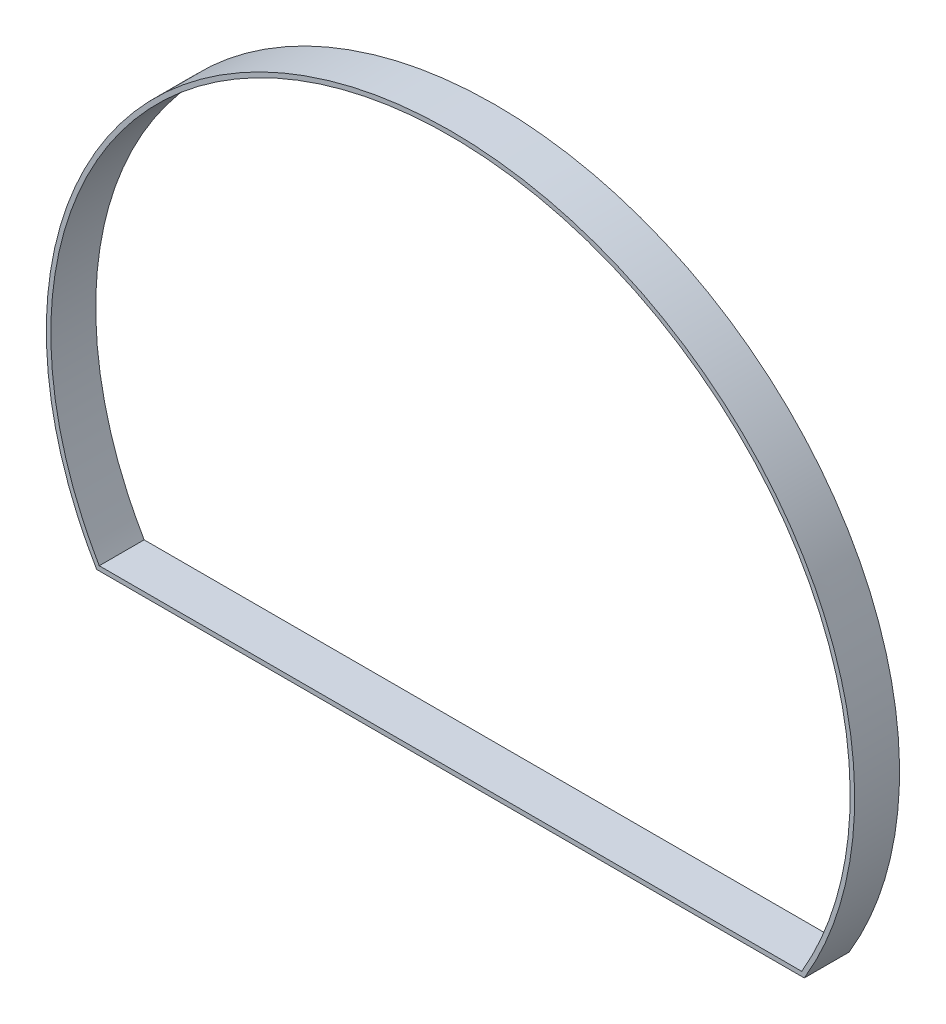
SolidWorks part; units mm, degrees
ref_plane "Front Plane" through (0, 0, 0) normal (0, 0, 1) x (1, 0, 0)
ref_plane "Top Plane" through (0, 0, 0) normal (0, 1, 0) x (1, 0, 0)
ref_plane "Right Plane" through (0, 0, 0) normal (1, 0, 0) x (0, 0, -1)
sketch "Sketch1" plane through (0, 0, 0) normal (0, 0, 1) x (1, 0, 0)
  line L0 (-87, -17.4103) -> (87, -17.4103) construction
  line L1 (-78.2136, -39.4103) -> (78.2136, -39.4103)
  line L2 (0, 0) -> (89, 0) construction
  line L3 (-78.7847, -40.4103) -> (78.7847, -40.4103)
  ellipse E0 centre (0, 0) end of major axis (89, 0) minor radius 82.5897 (78.2136, -39.4103) -> (-78.2136, -39.4103) ccw
  spline S0 degree 1 poles (78.7847, -40.4103) (-78.7847, -40.4103) knots 0 0 1 1 construction
  spline S1 degree 3 poles (78.7847, -40.4103) (80.6576, -37.2604) (83.991, -30.6822) (88.7458, -16.8884) (91.0082, 1.2326) (87.6166, 22.8878) (78.3582, 43.005) (63.8584, 60.2337) (45.0949, 73.4264) (23.3244, 81.7079) (0, 84.5305) (-23.3244, 81.7079) (-45.0949, 73.4264) (-63.8584, 60.2337) (-78.3582, 43.005) (-87.6166, 22.8878) (-91.0082, 1.2326) (-88.7458, -16.8884) (-83.991, -30.6822) (-80.6576, -37.2604) (-78.7847, -40.4103) knots -0.504194 -0.504194 -0.504194 -0.504194 -0.374508 -0.244821 0.014553 0.273927 0.533301 0.792675 1.052049 1.311422 1.570796 1.83017 2.089544 2.348918 2.608292 2.867666 3.127039 3.386413 3.5161 3.645787 3.645787 3.645787 3.645787
  dimension "D1" = 178
  dimension "D2" = 100
  dimension "D3" = 174
  dimension "D4" = 122
  dimension "D5" = 1
extrude "Boss-Extrude1" add sketch "Sketch1" along normal blind 10
